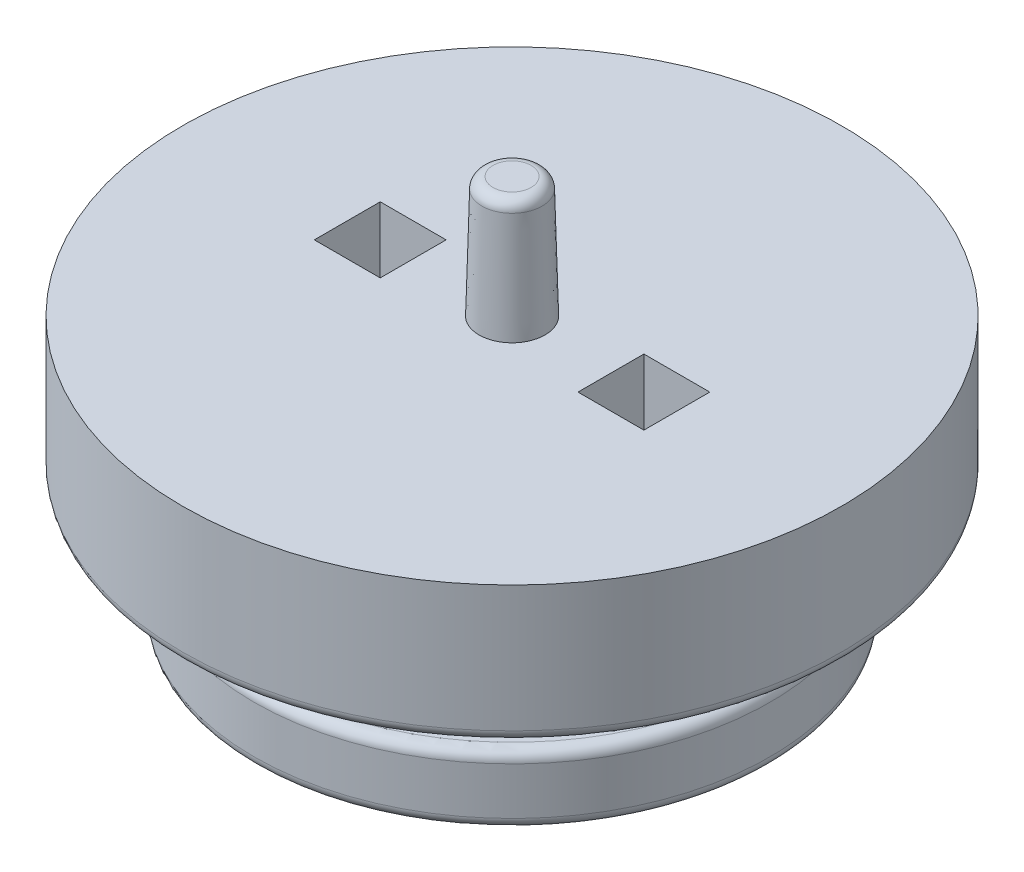
SolidWorks part; units mm, degrees
ref_plane "Front Plane" through (0, 0, 0) normal (0, 0, 1) x (1, 0, 0)
ref_plane "Top Plane" through (0, 0, 0) normal (0, 1, 0) x (1, 0, 0)
ref_plane "Right Plane" through (0, 0, 0) normal (1, 0, 0) x (0, 0, -1)
sketch "Sketch1" plane through (0, 0, 0) normal (0, 1, 0) x (1, 0, 0)
  circle A0 centre (0, 0) radius 5.75
  dimension "D1" = 11.5
extrude "Boss-Extrude1" add sketch "Sketch1" along normal blind 15
ref_plane "Plane1" through (0, 0, -5.75) normal (0, 0, -1) x (-1, 0, 0)
sketch "Sketch12" plane through (0, 15, 0) normal (0, 1, 0) x (1, 0, 0)
  circle A0 centre (0, 0) radius 5.75
  circle A1 centre (0, 0) radius 5.75 construction
extrude "Boss-Extrude3" add sketch "Sketch12" along normal blind 2
sketch "Sketch11" plane through (0, 17, 0) normal (0, 1, 0) x (1, 0, 0)
  line L0 (6, 0) -> (0, 0) construction
  line L1 (-7.5, 1.5) -> (-4.5, 1.5)
  line L2 (-7.5, 1.5) -> (-7.5, -1.5)
  line L3 (-7.5, -1.5) -> (-4.5, -1.5)
  line L4 (-4.5, 1.5) -> (-4.5, -1.5)
  line L5 (-7.5, 1.5) -> (-4.5, -1.5) construction
  line L6 (-7.5, -1.5) -> (-4.5, 1.5) construction
  line L7 (4.5, 1.5) -> (7.5, 1.5)
  line L8 (4.5, 1.5) -> (4.5, -1.5)
  line L9 (4.5, -1.5) -> (7.5, -1.5)
  line L10 (7.5, 1.5) -> (7.5, -1.5)
  line L11 (4.5, 1.5) -> (7.5, -1.5) construction
  line L12 (4.5, -1.5) -> (7.5, 1.5) construction
  line L13 (0, 0) -> (-6, 0) construction
  circle A0 centre (0, 0) radius 15
  point P0 (-6, 0)
  point P5 (6, 0)
  circle M22 centre (0, 0) radius 5.75
  dimension "D4" = 30
  dimension "D1" = 3
  dimension "D2" = 3
  dimension "D3" = 6
  dimension "D5" = 3
extrude "Boss-Extrude2" add sketch "Sketch11" along normal blind 4.25
sketch "Sketch13" plane through (0, 21.25, 0) normal (0, 1, 0) x (1, 0, 0)
  circle A0 centre (0, 0) radius 1.5
  dimension "D1" = 3
extrude "Boss-Extrude4" add sketch "Sketch13" along normal blind 5.5 draft 1.5
fillet "Fillet2" radius 0.5 1 edges at (0, 26.75, 1.356)
extrude "Boss-Extrude5" add sketch "Sketch11<2>" against normal blind 2 contours A0 L7 L10 L9 L3 L2 L1 M22 | L10 L7 L9 M22 | L2 L3 L1 M22 region at (-6.5911, 17, 0) region at (6.5911, 17, 0) region at (-14.5757, 17, 0)
sketch "Sketch11<2>" plane through (0, 17, 0) normal (0, 1, 0) x (1, 0, 0) same geometry as "Sketch11"
sketch "Sketch14" plane through (0, 0, 0) normal (0, -1, 0) x (1, 0, 0)
  circle A1 centre (0, 0) radius 11.75
  dimension "D1" = 23.5
extrude "Boss-Extrude6" add sketch "Sketch14" against normal offset from surface (12.4 mm away) 2.6 up to face at (0, 15, 5.75)
extrude "Cut-Extrude1" cut sketch "Sketch14<2>" against normal offset from surface (9.25 mm away) 3.15 up to face at (0, 12.4, 5.75)
sketch "Sketch14<2>" plane through (0, 0, 0) normal (0, -1, 0) x (1, 0, 0) same geometry as "Sketch14"
fillet "Fillet3" radius 0.5 3 edges at (0, 9.25, 11.75) (0, 12.4, 11.75) (0, 15, 15)
